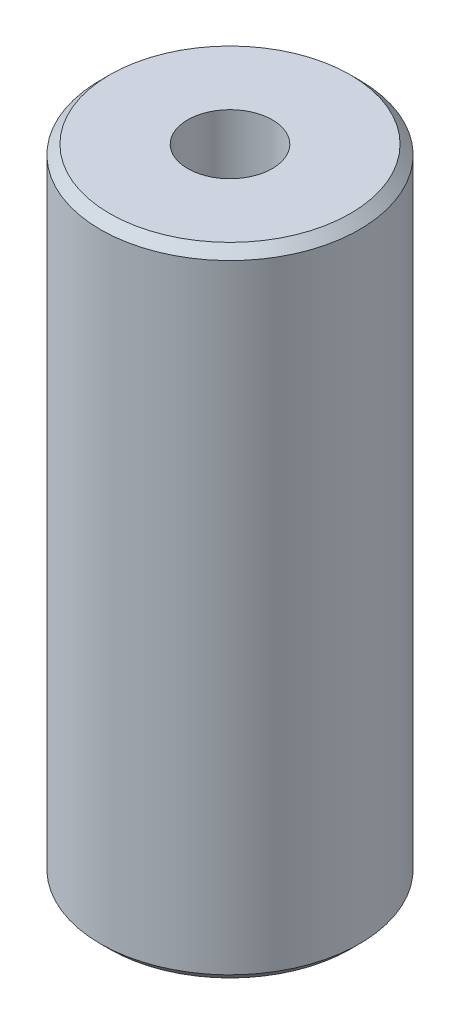
SolidWorks part; units mm, degrees
ref_plane "Front Plane" through (0, 0, 0) normal (0, 0, 1) x (1, 0, 0)
ref_plane "Top Plane" through (0, 0, 0) normal (0, 1, 0) x (1, 0, 0)
ref_plane "Right Plane" through (0, 0, 0) normal (1, 0, 0) x (0, 0, -1)
sketch "Sketch1" plane through (0, 0, 0) normal (0, 1, 0) x (1, 0, 0)
  circle A0 centre (0, 0) radius 45
  dimension "SHAFT_OD" = 90
extrude "Boss-Extrude1" add sketch "Sketch1" along normal blind 221.3663
sketch "Sketch2" plane through (0, 0, 0) normal (0, 1, 0) x (1, 0, 0)
  circle A0 centre (0, 0) radius 14.7055
  dimension "BORE_D" = 29.4109
extrude "Cut-Extrude1" cut sketch "Sketch2" along normal through all
chamfer "Chamfer1" distance 3.2075 angle 45 2 edges at (0, 221.3663, 45) (0, 0, 45)
